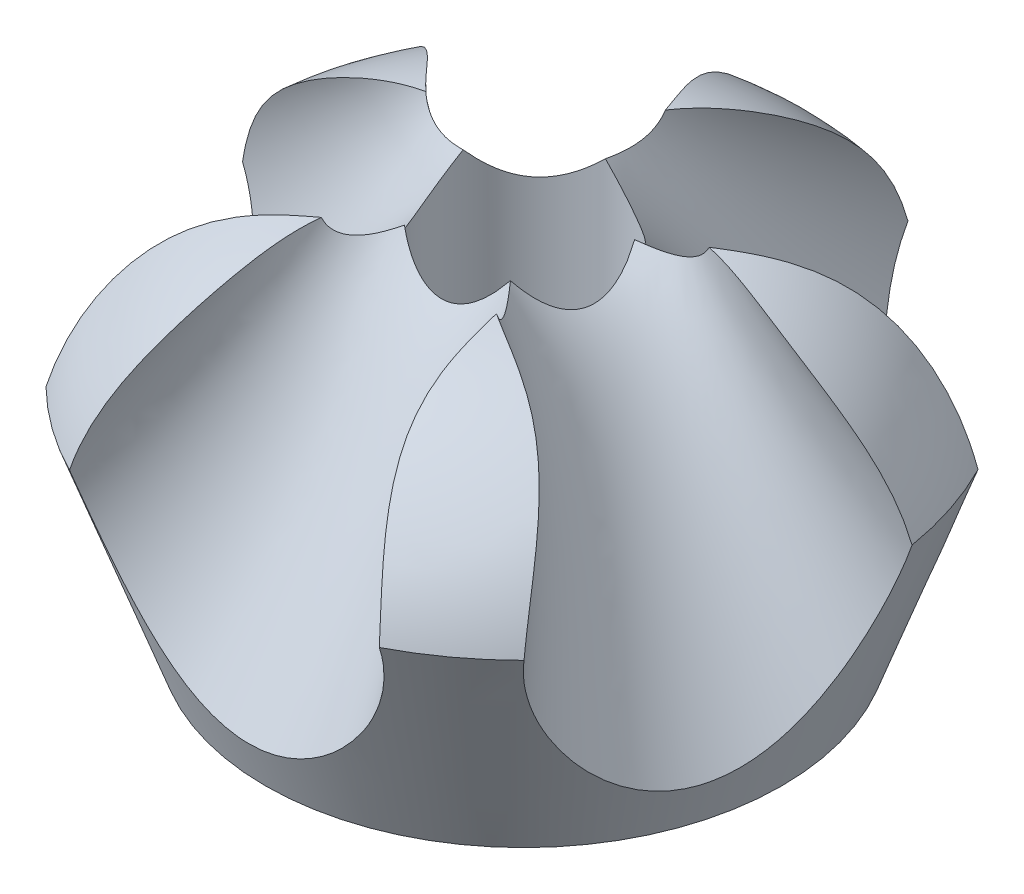
SolidWorks part; units mm, degrees
ref_plane "Front Plane" through (0, 0, 0) normal (0, 0, 1) x (1, 0, 0)
ref_plane "Top Plane" through (0, 0, 0) normal (0, 1, 0) x (1, 0, 0)
ref_plane "Right Plane" through (0, 0, 0) normal (1, 0, 0) x (0, 0, -1)
sketch "Sketch1" plane through (0, 0, 0) normal (0, 0, 1) x (1, 0, 0)
  line L0 (0, 0) -> (-15, 0)
  line L1 (-15, 0) -> (-19.6173, 12.6859)
  line L5 (0, 13) -> (0, 0)
  line L8 (0, 13) -> (0, 20.2524)
  arc A4 (-19.6173, 12.6859) -> (0, 20.2524) centre (-6.9751, 9.1227) cw
  point P8 (0, 27.7517)
  dimension "D1" = 15
  dimension "D2" = 13
  dimension "D3" = 13.5
  dimension "D6" = 110
revolve "Revolve1" add sketch "Sketch1" angle 360 about L5
ref_plane "Plane1" through (0, -4.8209, 13.2453) normal (0, -0.342, 0.9397) x (1, 0, 0)
sketch "Sketch4" plane through (0, -4.8209, 13.2453) normal (0, -0.342, 0.9397) x (1, 0, 0)
  circle A44 centre (0, 17.7606) radius 9.8847
sketch3d "3DSketch1"
  point P4 (0, 27.7517, 0)
sketch "Sketch5" plane through (0, 0, 0) normal (0, 1, 0) x (1, 0, 0)
  line L1 (3.5355, 3.5355) -> (-3.5355, 3.5355) construction
  line L2 (3.5355, 3.5355) -> (3.5355, -3.5355) construction
  line L3 (3.5355, -3.5355) -> (-3.5355, -3.5355) construction
  line L4 (-3.5355, 3.5355) -> (-3.5355, -3.5355) construction
  line L5 (3.5355, 3.5355) -> (-3.5355, -3.5355) construction
  line L6 (3.5355, -3.5355) -> (-3.5355, 3.5355) construction
  circle A0 centre (0, 0) radius 5
  dimension "D1" = 10
extrude "Cut-Extrude1" cut sketch "Sketch5" along normal up to next
sketch "Sketch6" plane through (0, 0, 0) normal (0, 1, 0) x (1, 0, 0)
  line L0 (0, 7.435) -> (0, -7.1989) construction
sketch "Sketch9" plane through (0, 0, 0) normal (0, 0, 1) x (1, 0, 0)
  circle A2 centre (0, 29.5835) radius 6.4357
loft "Cut-Loft1" cut profiles "Sketch9", "Sketch4" connector at (6.377, 30.4502, 0) connector at (0, 2.5801, 15.9391)
pattern_circular "CirPattern1" count 5 over 360 about axis through (0, 12.6859, 0) along (0, -1, 0) of "Cut-Loft1"
sketch "Sketch10" plane through (0, 0, 0) normal (0, 1, 0) x (1, 0, 0)
  line L1 (13.8715, -13.8715) -> (-13.8715, -13.8715)
  line L2 (13.8715, -13.8715) -> (13.8715, 13.8715)
  line L3 (13.8715, 13.8715) -> (-13.8715, 13.8715)
  line L4 (-13.8715, -13.8715) -> (-13.8715, 13.8715)
  line L5 (13.8715, -13.8715) -> (-13.8715, 13.8715) construction
  line L6 (13.8715, 13.8715) -> (-13.8715, -13.8715) construction
  circle A0 centre (0, 0) radius 19.6173 construction
